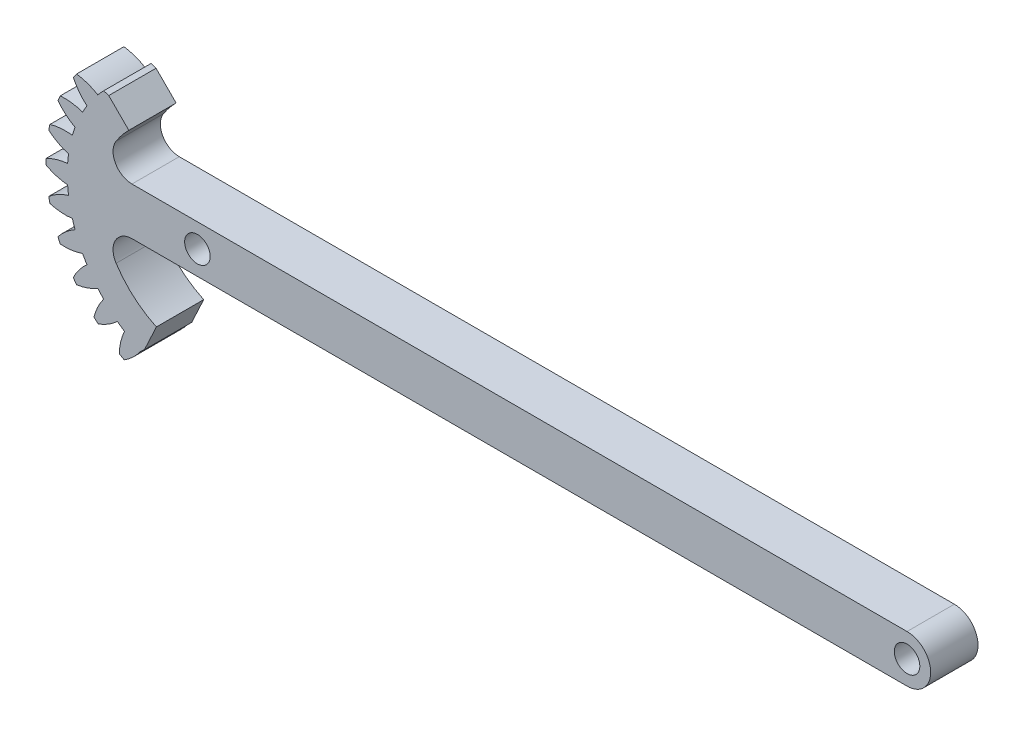
SolidWorks part; units mm, degrees
material "ABS"
ref_plane "Front Plane" through (0, 0, 0) normal (0, 0, 1) x (1, 0, 0)
ref_plane "Top Plane" through (0, 0, 0) normal (0, 1, 0) x (1, 0, 0)
ref_plane "Right Plane" through (0, 0, 0) normal (1, 0, 0) x (0, 0, -1)
ref_axis "X" through (-88.99, 0, 0) along (1, 0, 0)
ref_axis "Y" through (0, 55, 0) along (0, -1, 0)
ref_axis "Z" through (0, 0, -88.99) along (0, 0, 1)
sketch "Sketch1" plane through (0, 0, 0) normal (0, 0, 1) x (1, 0, 0)
  line L0 (0, 0) -> (150, 0) construction
  line L1 (0, 5) -> (150, 5)
  line L2 (0, -5) -> (150, -5)
  arc A0 (0, 5) -> (0, -5) centre (0, 0) ccw
  arc A1 (150, -5) -> (150, 5) centre (150, 0) ccw
  circle A2 centre (0, 0) radius 2.7
  circle A3 centre (150, 0) radius 2.7
  point P3 (75, 0)
  dimension "D1" = 5
  dimension "D3" = 5.4
  dimension "D2" = 150
extrude "Boss-Extrude1" add sketch "Sketch1" along normal mid plane 10
sketch "Sketch2" plane through (0, 0, 0) normal (0, 0, 1) x (1, 0, 0)
  line L0 (0, 5) -> (-19.8809, 5)
  line L1 (0, -5) -> (-19.8809, -5)
  line L2 (0, 0) -> (-14.4957, 14.4957) construction
  line L3 (0, 0) -> (-8.6637, -18.5793) construction
  line L4 (0, 0) -> (150, 0) construction
  line L5 (-14.4957, 14.4957) -> (-18.7383, 18.7383)
  line L6 (-8.6637, -18.5793) -> (-11.1994, -24.0172)
  arc A0 (-19.8809, 5) -> (-14.4957, 14.4957) centre (0, 0) cw
  arc A1 (-19.8809, -5) -> (-8.6637, -18.5793) centre (0, 0) ccw
  arc A3 (-18.7383, 18.7383) -> (-11.1994, -24.0172) centre (0, 0) ccw
  arc A4 (0, 5) -> (0, -5) centre (0, 0) ccw construction
  arc A5 (0, 5) -> (0, -5) centre (0, 0) ccw
  dimension "D1" = 135
  dimension "D3" = 20.5
  dimension "D2" = 110
  dimension "D4" = 6
extrude "Boss-Extrude2" add sketch "Sketch2" along normal up to surface and the other way up to surface up to face at (2.7, 0, 5) other way up to face at (75, 0, -5)
fillet "Fillet1" radius 4 2 edges at (-19.8809, 5, 0) (-19.8809, -5, 0)
sketch "Sketch3" plane through (0, 0, 0) normal (0, 0, 1) x (1, 0, 0)
  line L0 (-19.8097, 19.0728) -> (-18.7383, 18.7383)
  line L1 (-12.0177, -24.734) -> (-11.1994, -24.0172)
  arc A1 (-18.7383, 18.7383) -> (-11.1994, -24.0172) centre (0, 0) ccw construction
  arc A2 (-18.7383, 18.7383) -> (-11.1994, -24.0172) centre (0, 0) ccw
  arc A121 (-31.9943, -0.6021) -> (-27.4291, -1.9593) centre (-26.3602, 9.993) ccw
  arc A122 (-27.4291, -1.9593) -> (-27.2371, -3.7863) centre (0, 0) ccw
  arc A123 (-27.2371, -3.7863) -> (-31.4204, -6.063) centre (-23.7065, -15.2552) ccw
  arc A124 (-31.4204, -6.063) -> (-31.17, -7.241) centre (0, 0) ccw
  arc A125 (-31.17, -7.241) -> (-26.4224, -7.6193) centre (-27.8618, 4.294) ccw
  arc A126 (-26.4224, -7.6193) -> (-25.8547, -9.3665) centre (0, 0) ccw
  arc A127 (-25.8547, -9.3665) -> (-29.4732, -12.4632) centre (-20.0167, -19.8507) ccw
  arc A128 (-29.4732, -12.4632) -> (-28.9834, -13.5633) centre (0, 0) ccw
  arc A129 (-28.9834, -13.5633) -> (-24.2608, -12.9463) centre (-28.1458, -1.5926) ccw
  arc A130 (-24.2608, -12.9463) -> (-23.3423, -14.5373) centre (0, 0) ccw
  arc A131 (-23.3423, -14.5373) -> (-26.2379, -18.3187) centre (-15.4521, -23.5786) ccw
  arc A132 (-26.2379, -18.3187) -> (-25.53, -19.2929) centre (0, 0) ccw
  arc A133 (-25.53, -19.2929) -> (-21.039, -17.7075) centre (-27.1996, -7.4096) ccw
  arc A134 (-21.039, -17.7075) -> (-19.8097, -19.0728) centre (0, 0) ccw
  arc A135 (-19.8097, -19.0728) -> (-21.8559, -23.3735) centre (-10.2122, -26.2761) ccw
  arc A136 (-21.8559, -23.3735) -> (-20.9609, -24.1793) centre (0, 0) ccw
  arc A137 (-20.9609, -24.1793) -> (-16.8976, -21.6948) centre (-25.0647, -12.9028) ccw
  arc A138 (-16.8976, -21.6948) -> (-15.4114, -22.7747) centre (0, 0) ccw
  arc A139 (-15.4114, -22.7747) -> (-16.5186, -27.4068) centre (-4.5259, -27.8251) ccw
  arc A140 (-16.5186, -27.4068) -> (-15.4757, -28.009) centre (0, 0) ccw
  arc A141 (-15.4757, -28.009) -> (-12.0177, -24.734) centre (-21.8343, -17.8321) ccw
  arc A142 (-12.0177, -24.734) -> (-10.3395, -25.4812) centre (0, 0) ccw
  arc A143 (-10.3395, -25.4812) -> (-10.4594, -30.2424) centre (1.3582, -28.158) ccw
  arc A144 (-10.4594, -30.2424) -> (-9.3141, -30.6145) centre (0, 0) ccw
  arc A145 (-9.3141, -30.6145) -> (-6.6127, -26.6921) centre (-17.6497, -21.982) ccw
  arc A146 (-6.6127, -26.6921) -> (-4.8157, -27.074) centre (0, 0) ccw
  arc A147 (-4.8157, -27.074) -> (-3.9431, -31.7561) centre (7.1829, -27.2603) ccw
  arc A148 (-3.9431, -31.7561) -> (-2.7455, -31.882) centre (0, 0) ccw
  arc A149 (-2.7455, -31.882) -> (-0.9186, -27.4837) centre (-12.6936, -25.1712) ccw
  arc A150 (-0.9186, -27.4837) -> (0.9186, -27.4837) centre (0, 0) ccw
  arc A151 (0.9186, -27.4837) -> (2.7455, -31.882) centre (12.6936, -25.1712) ccw
  arc A152 (2.7455, -31.882) -> (3.9431, -31.7561) centre (0, 0) ccw
  arc A153 (3.9431, -31.7561) -> (4.8157, -27.074) centre (-7.1829, -27.2603) ccw
  arc A154 (4.8157, -27.074) -> (6.6127, -26.6921) centre (0, 0) ccw
  arc A155 (6.6127, -26.6921) -> (9.3141, -30.6145) centre (17.6497, -21.982) ccw
  arc A156 (9.3141, -30.6145) -> (10.4594, -30.2424) centre (0, 0) ccw
  arc A157 (10.4594, -30.2424) -> (10.3395, -25.4812) centre (-1.3582, -28.158) ccw
  arc A158 (10.3395, -25.4812) -> (12.0177, -24.734) centre (0, 0) ccw
  arc A159 (12.0177, -24.734) -> (15.4757, -28.009) centre (21.8343, -17.8321) ccw
  arc A160 (15.4757, -28.009) -> (16.5186, -27.4068) centre (0, 0) ccw
  arc A161 (16.5186, -27.4068) -> (15.4114, -22.7747) centre (4.5259, -27.8251) ccw
  arc A162 (15.4114, -22.7747) -> (16.8976, -21.6948) centre (0, 0) ccw
  arc A163 (16.8976, -21.6948) -> (20.9609, -24.1793) centre (25.0647, -12.9028) ccw
  arc A164 (20.9609, -24.1793) -> (21.8559, -23.3735) centre (0, 0) ccw
  arc A165 (21.8559, -23.3735) -> (19.8097, -19.0728) centre (10.2122, -26.2761) ccw
  arc A166 (19.8097, -19.0728) -> (21.039, -17.7075) centre (0, 0) ccw
  arc A167 (21.039, -17.7075) -> (25.53, -19.2929) centre (27.1996, -7.4096) ccw
  arc A168 (25.53, -19.2929) -> (26.2379, -18.3187) centre (0, 0) ccw
  arc A169 (26.2379, -18.3187) -> (23.3423, -14.5373) centre (15.4521, -23.5786) ccw
  arc A170 (23.3423, -14.5373) -> (24.2608, -12.9463) centre (0, 0) ccw
  arc A171 (24.2608, -12.9463) -> (28.9834, -13.5633) centre (28.1458, -1.5926) ccw
  arc A172 (28.9834, -13.5633) -> (29.4732, -12.4632) centre (0, 0) ccw
  arc A173 (29.4732, -12.4632) -> (25.8547, -9.3665) centre (20.0167, -19.8507) ccw
  arc A174 (25.8547, -9.3665) -> (26.4224, -7.6193) centre (0, 0) ccw
  arc A175 (26.4224, -7.6193) -> (31.17, -7.241) centre (27.8618, 4.294) ccw
  arc A176 (31.17, -7.241) -> (31.4204, -6.063) centre (0, 0) ccw
  arc A177 (31.4204, -6.063) -> (27.2371, -3.7863) centre (23.7065, -15.2552) ccw
  arc A178 (27.2371, -3.7863) -> (27.4291, -1.9593) centre (0, 0) ccw
  arc A179 (27.4291, -1.9593) -> (31.9943, -0.6021) centre (26.3602, 9.993) ccw
  arc A180 (31.9943, -0.6021) -> (31.9943, 0.6021) centre (0, 0) ccw
  arc A181 (31.9943, 0.6021) -> (27.4291, 1.9593) centre (26.3602, -9.993) ccw
  arc A182 (27.4291, 1.9593) -> (27.2371, 3.7863) centre (0, 0) ccw
  arc A183 (27.2371, 3.7863) -> (31.4204, 6.063) centre (23.7065, 15.2552) ccw
  arc A184 (31.4204, 6.063) -> (31.17, 7.241) centre (0, 0) ccw
  arc A185 (31.17, 7.241) -> (26.4224, 7.6193) centre (27.8618, -4.294) ccw
  arc A186 (26.4224, 7.6193) -> (25.8547, 9.3665) centre (0, 0) ccw
  arc A187 (25.8547, 9.3665) -> (29.4732, 12.4632) centre (20.0167, 19.8507) ccw
  arc A188 (29.4732, 12.4632) -> (28.9834, 13.5633) centre (0, 0) ccw
  arc A189 (28.9834, 13.5633) -> (24.2608, 12.9463) centre (28.1458, 1.5926) ccw
  arc A190 (24.2608, 12.9463) -> (23.3423, 14.5373) centre (0, 0) ccw
  arc A191 (23.3423, 14.5373) -> (26.2379, 18.3187) centre (15.4521, 23.5786) ccw
  arc A192 (26.2379, 18.3187) -> (25.53, 19.2929) centre (0, 0) ccw
  arc A193 (25.53, 19.2929) -> (21.039, 17.7075) centre (27.1996, 7.4096) ccw
  arc A194 (21.039, 17.7075) -> (19.8097, 19.0728) centre (0, 0) ccw
  arc A195 (19.8097, 19.0728) -> (21.8559, 23.3735) centre (10.2122, 26.2761) ccw
  arc A196 (21.8559, 23.3735) -> (20.9609, 24.1793) centre (0, 0) ccw
  arc A197 (20.9609, 24.1793) -> (16.8976, 21.6948) centre (25.0647, 12.9028) ccw
  arc A198 (16.8976, 21.6948) -> (15.4114, 22.7747) centre (0, 0) ccw
  arc A199 (15.4114, 22.7747) -> (16.5186, 27.4068) centre (4.5259, 27.8251) ccw
  arc A200 (16.5186, 27.4068) -> (15.4757, 28.009) centre (0, 0) ccw
  arc A201 (15.4757, 28.009) -> (12.0177, 24.734) centre (21.8343, 17.8321) ccw
  arc A202 (12.0177, 24.734) -> (10.3395, 25.4812) centre (0, 0) ccw
  arc A203 (10.3395, 25.4812) -> (10.4594, 30.2424) centre (-1.3582, 28.158) ccw
  arc A204 (10.4594, 30.2424) -> (9.3141, 30.6145) centre (0, 0) ccw
  arc A205 (9.3141, 30.6145) -> (6.6127, 26.6921) centre (17.6497, 21.982) ccw
  arc A206 (6.6127, 26.6921) -> (4.8157, 27.074) centre (0, 0) ccw
  arc A207 (4.8157, 27.074) -> (3.9431, 31.7561) centre (-7.1829, 27.2603) ccw
  arc A208 (3.9431, 31.7561) -> (2.7455, 31.882) centre (0, 0) ccw
  arc A209 (2.7455, 31.882) -> (0.9186, 27.4837) centre (12.6936, 25.1712) ccw
  arc A210 (0.9186, 27.4837) -> (-0.9186, 27.4837) centre (0, 0) ccw
  arc A211 (-0.9186, 27.4837) -> (-2.7455, 31.882) centre (-12.6936, 25.1712) ccw
  arc A212 (-2.7455, 31.882) -> (-3.9431, 31.7561) centre (0, 0) ccw
  arc A213 (-3.9431, 31.7561) -> (-4.8157, 27.074) centre (7.1829, 27.2603) ccw
  arc A214 (-4.8157, 27.074) -> (-6.6127, 26.6921) centre (0, 0) ccw
  arc A215 (-6.6127, 26.6921) -> (-9.3141, 30.6145) centre (-17.6497, 21.982) ccw
  arc A216 (-9.3141, 30.6145) -> (-10.4594, 30.2424) centre (0, 0) ccw
  arc A217 (-10.4594, 30.2424) -> (-10.3395, 25.4812) centre (1.3582, 28.158) ccw
  arc A218 (-10.3395, 25.4812) -> (-12.0177, 24.734) centre (0, 0) ccw
  arc A219 (-12.0177, 24.734) -> (-15.4757, 28.009) centre (-21.8343, 17.8321) ccw
  arc A220 (-15.4757, 28.009) -> (-16.5186, 27.4068) centre (0, 0) ccw
  arc A221 (-16.5186, 27.4068) -> (-15.4114, 22.7747) centre (-4.5259, 27.8251) ccw
  arc A222 (-15.4114, 22.7747) -> (-16.8976, 21.6948) centre (0, 0) ccw
  arc A223 (-16.8976, 21.6948) -> (-20.9609, 24.1793) centre (-25.0647, 12.9028) ccw
  arc A224 (-20.9609, 24.1793) -> (-21.8559, 23.3735) centre (0, 0) ccw
  arc A225 (-21.8559, 23.3735) -> (-19.8097, 19.0728) centre (-10.2122, 26.2761) ccw
  arc A226 (-19.8097, 19.0728) -> (-21.039, 17.7075) centre (0, 0) ccw
  arc A227 (-21.039, 17.7075) -> (-25.53, 19.2929) centre (-27.1996, 7.4096) ccw
  arc A228 (-25.53, 19.2929) -> (-26.2379, 18.3187) centre (0, 0) ccw
  arc A229 (-26.2379, 18.3187) -> (-23.3423, 14.5373) centre (-15.4521, 23.5786) ccw
  arc A230 (-23.3423, 14.5373) -> (-24.2608, 12.9463) centre (0, 0) ccw
  arc A231 (-24.2608, 12.9463) -> (-28.9834, 13.5633) centre (-28.1458, 1.5926) ccw
  arc A232 (-28.9834, 13.5633) -> (-29.4732, 12.4632) centre (0, 0) ccw
  arc A233 (-29.4732, 12.4632) -> (-25.8547, 9.3665) centre (-20.0167, 19.8507) ccw
  arc A234 (-25.8547, 9.3665) -> (-26.4224, 7.6193) centre (0, 0) ccw
  arc A235 (-26.4224, 7.6193) -> (-31.17, 7.241) centre (-27.8618, -4.294) ccw
  arc A236 (-31.17, 7.241) -> (-31.4204, 6.063) centre (0, 0) ccw
  arc A237 (-31.4204, 6.063) -> (-27.2371, 3.7863) centre (-23.7065, 15.2552) ccw
  arc A238 (-27.2371, 3.7863) -> (-27.4291, 1.9593) centre (0, 0) ccw
  arc A239 (-27.4291, 1.9593) -> (-31.9943, 0.6021) centre (-26.3602, -9.993) ccw
  arc A240 (-31.9943, 0.6021) -> (-31.9943, -0.6021) centre (0, 0) ccw
  arc A241 (-31.9943, -0.6021) -> (-27.4291, -1.9593) centre (-26.3602, 9.993) ccw
  arc A242 (-27.4291, -1.9593) -> (-27.2371, -3.7863) centre (0, 0) ccw
  arc A243 (-27.2371, -3.7863) -> (-31.4204, -6.063) centre (-23.7065, -15.2552) ccw
  arc A244 (-31.4204, -6.063) -> (-31.17, -7.241) centre (0, 0) ccw
  arc A245 (-31.17, -7.241) -> (-26.4224, -7.6193) centre (-27.8618, 4.294) ccw
  arc A246 (-26.4224, -7.6193) -> (-25.8547, -9.3665) centre (0, 0) ccw
  arc A247 (-25.8547, -9.3665) -> (-29.4732, -12.4632) centre (-20.0167, -19.8507) ccw
  arc A248 (-29.4732, -12.4632) -> (-28.9834, -13.5633) centre (0, 0) ccw
  arc A249 (-28.9834, -13.5633) -> (-24.2608, -12.9463) centre (-28.1458, -1.5926) ccw
  arc A250 (-24.2608, -12.9463) -> (-23.3423, -14.5373) centre (0, 0) ccw
  arc A251 (-23.3423, -14.5373) -> (-26.2379, -18.3187) centre (-15.4521, -23.5786) ccw
  arc A252 (-26.2379, -18.3187) -> (-25.53, -19.2929) centre (0, 0) ccw
  arc A253 (-25.53, -19.2929) -> (-21.039, -17.7075) centre (-27.1996, -7.4096) ccw
  arc A254 (-21.039, -17.7075) -> (-19.8097, -19.0728) centre (0, 0) ccw
  arc A255 (-19.8097, -19.0728) -> (-21.8559, -23.3735) centre (-10.2122, -26.2761) ccw
  arc A256 (-21.8559, -23.3735) -> (-20.9609, -24.1793) centre (0, 0) ccw
  arc A257 (-20.9609, -24.1793) -> (-16.8976, -21.6948) centre (-25.0647, -12.9028) ccw
  arc A258 (-16.8976, -21.6948) -> (-15.4114, -22.7747) centre (0, 0) ccw
  arc A259 (-15.4114, -22.7747) -> (-16.5186, -27.4068) centre (-4.5259, -27.8251) ccw
  arc A260 (-16.5186, -27.4068) -> (-15.4757, -28.009) centre (0, 0) ccw
  arc A261 (-15.4757, -28.009) -> (-12.0177, -24.734) centre (-21.8343, -17.8321) ccw
  arc A346 (-19.8097, 19.0728) -> (-21.039, 17.7075) centre (0, 0) ccw
  arc A347 (-21.039, 17.7075) -> (-25.53, 19.2929) centre (-27.1996, 7.4096) ccw
  arc A348 (-25.53, 19.2929) -> (-26.2379, 18.3187) centre (0, 0) ccw
  arc A349 (-26.2379, 18.3187) -> (-23.3423, 14.5373) centre (-15.4521, 23.5786) ccw
  arc A350 (-23.3423, 14.5373) -> (-24.2608, 12.9463) centre (0, 0) ccw
  arc A351 (-24.2608, 12.9463) -> (-28.9834, 13.5633) centre (-28.1458, 1.5926) ccw
  arc A352 (-28.9834, 13.5633) -> (-29.4732, 12.4632) centre (0, 0) ccw
  arc A353 (-29.4732, 12.4632) -> (-25.8547, 9.3665) centre (-20.0167, 19.8507) ccw
  arc A354 (-25.8547, 9.3665) -> (-26.4224, 7.6193) centre (0, 0) ccw
  arc A355 (-26.4224, 7.6193) -> (-31.17, 7.241) centre (-27.8618, -4.294) ccw
  arc A356 (-31.17, 7.241) -> (-31.4204, 6.063) centre (0, 0) ccw
  arc A357 (-31.4204, 6.063) -> (-27.2371, 3.7863) centre (-23.7065, 15.2552) ccw
  arc A358 (-27.2371, 3.7863) -> (-27.4291, 1.9593) centre (0, 0) ccw
  arc A359 (-27.4291, 1.9593) -> (-31.9943, 0.6021) centre (-26.3602, -9.993) ccw
  arc A360 (-31.9943, 0.6021) -> (-31.9943, -0.6021) centre (0, 0) ccw
  dimension "D1" = 0
extrude "Boss-Extrude3" add sketch "Sketch3" along normal up to surface and the other way up to surface up to face at (2.7, 0, 5) other way up to face at (17.4467, -1.1852, -5)
